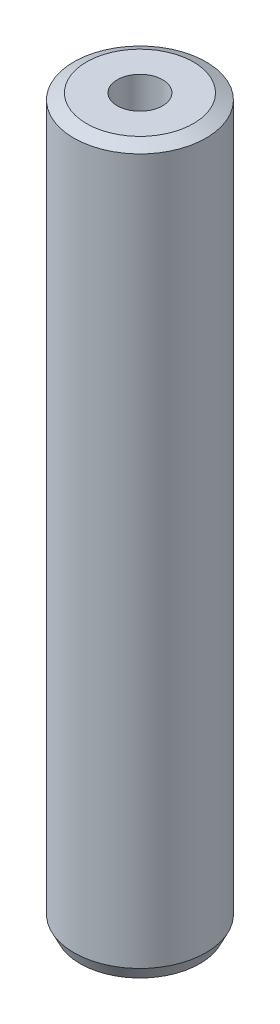
SolidWorks part; units mm, degrees
ref_plane "Front Plane" through (0, 0, 0) normal (0, 0, 1) x (1, 0, 0)
ref_plane "Top Plane" through (0, 0, 0) normal (0, 1, 0) x (1, 0, 0)
ref_plane "Right Plane" through (0, 0, 0) normal (1, 0, 0) x (0, 0, -1)
sketch "Sketch1" plane through (0, 0, 0) normal (0, 1, 0) x (1, 0, 0)
  circle A0 centre (0, 0) radius 30
  dimension "SHAFT_OD" = 60
extrude "Boss-Extrude1" add sketch "Sketch1" along normal blind 328.6873
sketch "Sketch2" plane through (0, 0, 0) normal (0, 1, 0) x (1, 0, 0)
  circle A0 centre (0, 0) radius 10.2741
  dimension "BORE_D" = 20.5482
extrude "Cut-Extrude1" cut sketch "Sketch2" along normal through all
chamfer "Chamfer1" distance 2.8316 angle 63.793 2 edges at (0, 328.6873, 30) (0, 0, 30) first distance on face at (0, 328.6873, 30) first distance on face at (0, 0, 10.2741)
